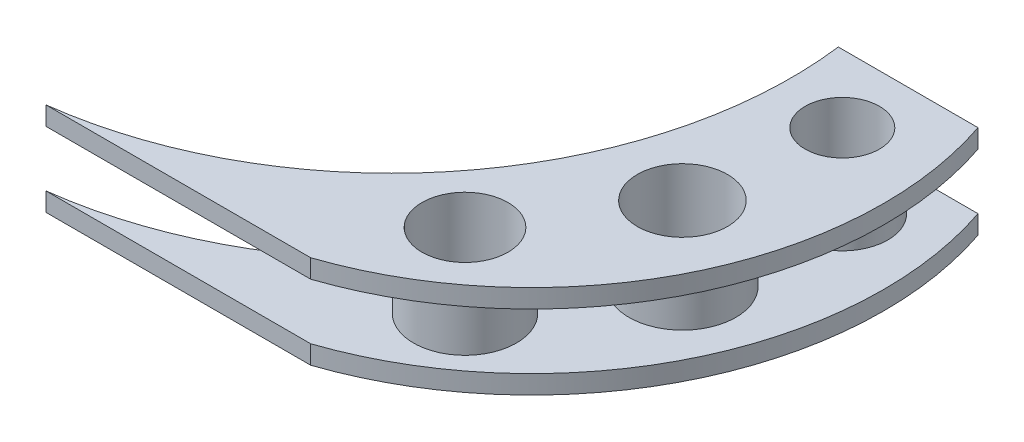
SolidWorks part; units mm, degrees
ref_plane "Front Plane" through (0, 0, 0) normal (0, 0, 1) x (1, 0, 0)
ref_plane "Top Plane" through (0, 0, 0) normal (0, 1, 0) x (1, 0, 0)
ref_plane "Right Plane" through (0, 0, 0) normal (1, 0, 0) x (0, 0, -1)
sketch "Sketch1" plane through (0, 0, 0) normal (0, 1, 0) x (1, 0, 0)
  line L0 (164.2612, 12.0214) -> (227.7612, 12.0214)
  line L1 (6.9747, -190.8615) -> (127.3147, -190.8615)
  arc A0 (164.2612, 12.0214) -> (6.9747, -190.8615) centre (-15.8235, -10.7768) cw
  arc A1 (227.7612, 12.0214) -> (127.3147, -190.8615) centre (76.0966, -39.1968) cw
  dimension "D1" = 63.5
extrude "Boss-Extrude1" add sketch "Sketch1" along normal blind 8.4667
sketch "Sketch2" plane through (0, 8.4667, 0) normal (0, 1, 0) x (1, 0, 0)
  circle A0 centre (196.951, -18.8516) radius 20.6954
  circle A1 centre (189.2596, -83.8438) radius 24.3223
  circle A2 centre (150.4181, -143.8366) radius 23.3829
  circle A3 centre (196.951, -18.8516) radius 16.8854
  circle A4 centre (189.2596, -83.8438) radius 20.5123
  circle A5 centre (150.4181, -143.8366) radius 19.5729
  dimension "D1" = 3.81
extrude "Cut-Extrude3" cut sketch "Sketch2" against normal through all contours A3 | A4 | A5
extrude "Boss-Extrude2" add sketch "Sketch2<4>" along normal blind 12.7 contours A5 | A2 | A4 | A1 | A3 | A0
sketch "Sketch2<4>" plane through (0, 8.4667, 0) normal (0, 1, 0) x (1, 0, 0) same geometry as "Sketch2"
ref_plane "Plane1" through (0, 21.1667, 0) normal (0, 1, 0) x (1, 0, 0)
mirror "Mirror3" about plane through (0, 21.1667, 0) normal (0, 1, 0) of "Boss-Extrude2", "Cut-Extrude3", "Boss-Extrude1"
